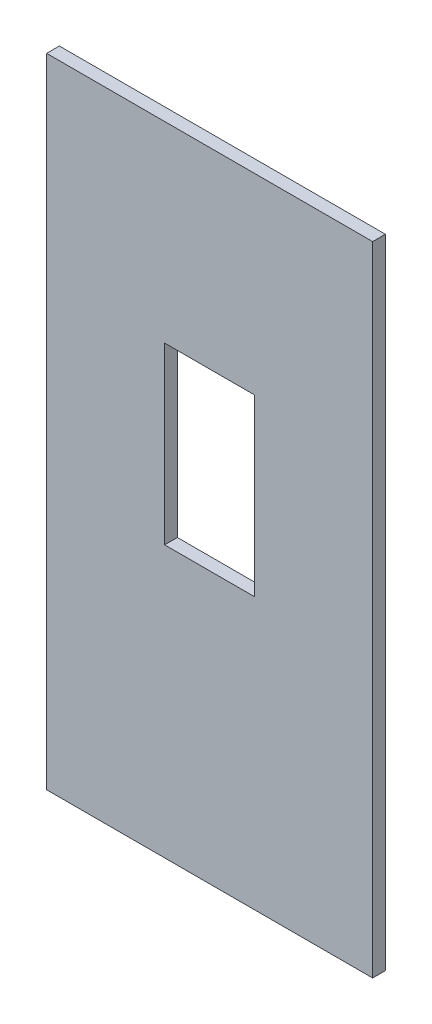
SolidWorks part; units mm, degrees
ref_plane "Front Plane" through (0, 0, 0) normal (0, 0, 1) x (1, 0, 0)
ref_plane "Top Plane" through (0, 0, 0) normal (0, 1, 0) x (1, 0, 0)
ref_plane "Right Plane" through (0, 0, 0) normal (1, 0, 0) x (0, 0, -1)
sketch "Sketch1" plane through (0, 0, 0) normal (0, 0, 1) x (1, 0, 0)
  line L1 (40.64, -79.502) -> (-40.64, -79.502)
  line L2 (40.64, -79.502) -> (40.64, 79.502)
  line L3 (40.64, 79.502) -> (-40.64, 79.502)
  line L4 (-40.64, -79.502) -> (-40.64, 79.502)
  line L5 (40.64, -79.502) -> (-40.64, 79.502) construction
  line L6 (40.64, 79.502) -> (-40.64, -79.502) construction
  point P0 (0, 0)
  dimension "D1" = 81.28
  dimension "D2" = 79.502
extrude "Boss-Extrude1" add sketch "Sketch1" along normal blind 3.175
ref_axis "Axis1" through (0, 0, 0) along (0, 0, 1)
sketch "Sketch3" plane through (0, 0, 3.175) normal (0, 0, 1) x (1, 0, 0)
  line L1 (-11.2262, 31.6582) -> (11.2262, 31.6582)
  line L2 (-11.2262, 31.6582) -> (-11.2262, -11.9062)
  line L3 (-11.2262, -11.9062) -> (11.2262, -11.9062)
  line L4 (11.2262, 31.6582) -> (11.2262, -11.9062)
  point P4 (0, 31.6582)
  dimension "D1" = 22.4524
  dimension "D2" = 43.5644
  dimension "D3" = 31.6582
extrude "Cut-Extrude1" cut sketch "Sketch3" against normal up to next
